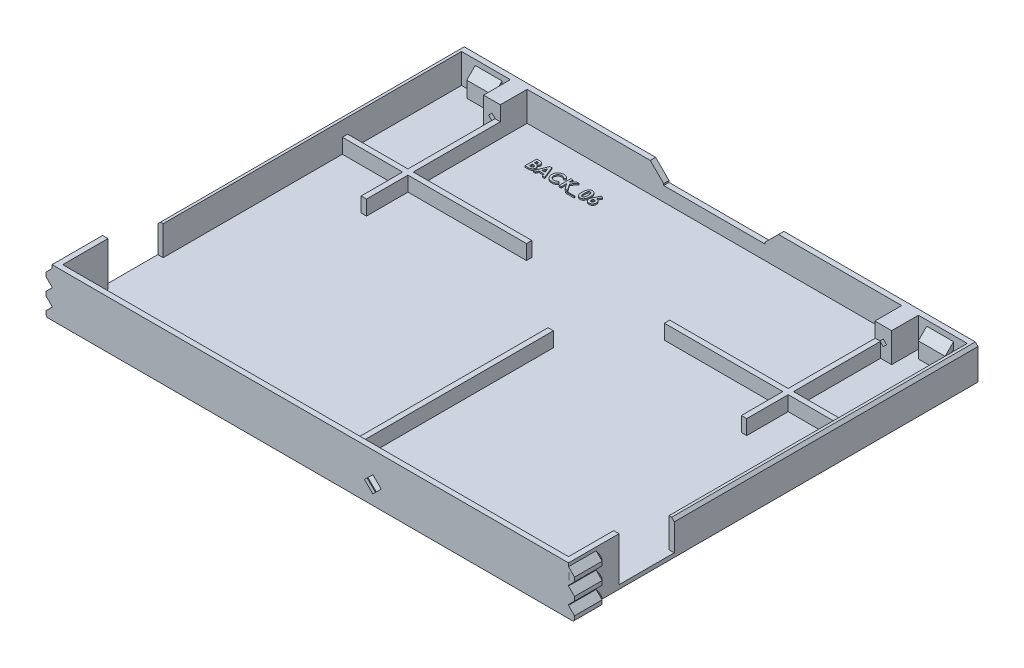
SolidWorks part; units mm, degrees
ref_plane "Front Plane" through (0, 0, 0) normal (0, 0, 1) x (1, 0, 0)
ref_plane "Top Plane" through (0, 0, 0) normal (0, 1, 0) x (1, 0, 0)
ref_plane "Right Plane" through (0, 0, 0) normal (1, 0, 0) x (0, 0, -1)
sketch "Sketch1" plane through (0, 0, 0) normal (0, 1, 0) x (1, 0, 0)
  line L3 (-77.15, -61.17) -> (77.15, -61.17)
  line L5 (-77.15, 61.17) -> (77.15, -61.17) construction
  line L6 (-77.15, -61.17) -> (77.15, 61.17) construction
  line L13 (-77.15, 61.17) -> (-77.15, -61.17)
  line L18 (77.15, 61.17) -> (-77.15, 61.17)
  line L20 (77.15, 61.17) -> (77.15, -61.17)
  point P0 (0, 0)
  point P6 (0, 0)
  dimension "D3" = 154.3
  dimension "D1" = 154.3
  dimension "D2" = 122.34
extrude "flat_on_wall" add sketch "Sketch1" along normal blind 1.2
sketch "Sketch3" plane through (0, 0, 0) normal (0, 1, 0) x (1, 0, 0)
  line L0 (-77.15, -29.57) -> (-77.15, 61.17)
  line L1 (-77.15, 61.17) -> (-77.15, -61.17) construction
  line L2 (-77.15, 61.17) -> (-45.55, 61.17)
  line L3 (77.15, 61.17) -> (-77.15, 61.17) construction
  line L6 (-75.55, 59.57) -> (-75.55, -29.57)
  line L7 (-75.55, -29.57) -> (-77.15, -29.57)
  line L8 (45.55, 61.17) -> (77.15, 61.17)
  line L9 (77.15, 61.17) -> (77.15, -29.57)
  line L10 (77.15, -61.17) -> (77.15, 61.17) construction
  line L11 (77.15, -29.57) -> (75.55, -29.57)
  line L12 (75.55, -29.57) -> (75.55, 59.57)
  line L15 (-77.15, -46.07) -> (-77.15, -61.17)
  line L16 (-77.15, -61.17) -> (77.15, -61.17)
  line L17 (77.15, -61.17) -> (77.15, -46.07)
  line L18 (77.15, -46.07) -> (75.55, -46.07)
  line L19 (75.55, -46.07) -> (75.55, -59.57)
  line L20 (75.55, -59.57) -> (-75.55, -59.57)
  line L21 (-75.55, -59.57) -> (-75.55, -46.07)
  line L22 (-75.55, -46.07) -> (-77.15, -46.07)
  line L23 (-75.55, 59.57) -> (-60.95, 59.57)
  line L24 (-60.95, 59.57) -> (-60.95, 51.57)
  line L25 (-60.95, 51.57) -> (-55.95, 51.57)
  line L26 (-55.95, 51.57) -> (-55.95, 59.57)
  line L27 (-55.95, 59.57) -> (-45.55, 59.57)
  line L28 (75.55, 59.57) -> (60.95, 59.57)
  line L29 (60.95, 59.57) -> (60.95, 51.57)
  line L30 (60.95, 51.57) -> (55.95, 51.57)
  line L31 (55.95, 51.57) -> (55.95, 59.57)
  line L32 (55.95, 59.57) -> (45.55, 59.57)
  line L34 (-45.55, 59.57) -> (45.55, 59.57)
  line L36 (-45.55, 61.17) -> (45.55, 61.17)
  point P25 (-76.35, -46.07)
  dimension "D2" = 1.6
  dimension "D3" = 30
  dimension "D4" = 16.5
  dimension "D5" = 5
  dimension "D6" = 1.6
  dimension "D7" = 30
  dimension "D8" = 16.5
  dimension "D9" = 1.6
  dimension "D10" = 13.5
  dimension "D11" = 1.6
  dimension "D12" = 1.6
  dimension "D13" = 13.5
  dimension "D14" = 14.6
  dimension "D15" = 5
  dimension "D16" = 8
  dimension "D17" = 8
  dimension "D18" = 8
  dimension "D19" = 8
  dimension "D20" = 1.6
  dimension "D21" = 14.6
  dimension "D22" = 1.6
  dimension "D23" = 1.6
extrude "walls" add sketch "Sketch3" along normal blind 10
sketch "Sketch5" plane through (0, 0, 0) normal (1, 0, 0) x (0, 0, -1)
  line L0 (-61.17, 10) -> (-61.17, 0) construction
  line L5 (-61.17, 0) -> (-51.97, 0)
  line L6 (-61.17, 0) -> (-61.17, 2)
  line L7 (-61.17, 2) -> (-51.97, 2)
  line L8 (-51.97, 0) -> (-51.97, 2)
  line L9 (-61.17, 0) -> (61.17, 0) construction
  line L10 (-61.17, 10) -> (-51.97, 10)
  line L11 (-61.17, 5) -> (-51.97, 5)
  line L12 (-61.17, 5) -> (-61.17, 7)
  line L13 (-61.17, 7) -> (-51.97, 7)
  line L14 (-51.97, 5) -> (-51.97, 7)
  line L15 (-61.17, 10) -> (-61.17, 12)
  line L16 (-61.17, 12) -> (-51.97, 12)
  line L17 (-51.97, 10) -> (-51.97, 12)
  line L18 (-61.17, 10) -> (-46.07, 10) construction
  dimension "D1" = 0
  dimension "D2" = 9.2
  dimension "D3" = 2
  dimension "D4" = 9.2
  dimension "D5" = 2
  dimension "D6" = 3
  dimension "D7" = 2
extrude "rails" add sketch "Sketch5" along normal blind 0.75 from surface starting at face at (77.15, 5.3, 18.91)
sketch "Sketch6" plane through (0, 0, 0) normal (1, 0, 0) x (0, 0, -1)
  line L0 (-61.17, 12) -> (-51.97, 12)
  line L1 (-61.17, 2) -> (-51.97, 2)
  line L2 (-61.17, 2) -> (-61.17, 0)
  line L3 (-61.17, 0) -> (-51.97, 0)
  line L4 (-51.97, 2) -> (-51.97, 0)
  line L5 (-61.17, 7) -> (-51.97, 7)
  line L6 (-61.17, 7) -> (-61.17, 5)
  line L7 (-61.17, 5) -> (-51.97, 5)
  line L8 (-51.97, 7) -> (-51.97, 5)
  line L9 (-61.17, 12) -> (-61.17, 10)
  line L10 (-61.17, 10) -> (-51.97, 10)
  line L11 (-51.97, 12) -> (-51.97, 10)
  dimension "D1" = 9.2
  dimension "D2" = 9.2
  dimension "D3" = 2
  dimension "D4" = 2
  dimension "D5" = 2
extrude "rails-left" add sketch "Sketch6" along normal blind 0.1 and the other way blind 1.8 from surface starting at face at (-77.15, 5.3, 18.91)
sketch "Sketch7" plane through (0, 0, 0) normal (0, 1, 0) x (1, 0, 0)
  line L0 (-47.15, 46.17) -> (-47.15, 39.9043) construction
  line L1 (-44.69, 46.17) -> (-44.69, 43.37)
  line L2 (-49.61, 46.17) -> (-49.61, 43.37)
  line L3 (77.15, 61.17) -> (-77.15, 61.17) construction
  line L4 (-77.15, -29.57) -> (-77.15, -46.07) construction
  line L5 (47.15, 46.17) -> (47.15, 39.9043) construction
  line L6 (49.61, 46.17) -> (49.61, 43.37)
  line L7 (44.69, 46.17) -> (44.69, 43.37)
  line L9 (77.15, -29.57) -> (77.15, 61.17) construction
  line L10 (77.15, 61.17) -> (-77.15, 61.17) construction
  line L13 (-77.05, -61.17) -> (77.15, -61.17) construction
  line L14 (-0.45, 8.83) -> (-0.45, 2.5643) construction
  line L15 (2.01, 8.83) -> (2.01, 6.03)
  line L16 (-2.91, 8.83) -> (-2.91, 6.03)
  line L17 (77.15, -46.07) -> (77.15, -29.57) construction
  arc A0 (-44.69, 46.17) -> (-49.61, 46.17) centre (-47.15, 46.17) ccw
  arc A3 (-44.69, 43.37) -> (-49.61, 43.37) centre (-47.15, 39.9043) cw
  arc A4 (49.61, 46.17) -> (44.69, 46.17) centre (47.15, 46.17) ccw
  arc A5 (49.61, 43.37) -> (44.69, 43.37) centre (47.15, 39.9043) cw
  arc A8 (2.01, 8.83) -> (-2.91, 8.83) centre (-0.45, 8.83) ccw
  arc A9 (2.01, 6.03) -> (-2.91, 6.03) centre (-0.45, 2.5643) cw
  point P2 (-47.9176, 44.8712)
  point P13 (43.1175, 41.9506)
  dimension "D1" = 15
  dimension "D5" = 2.46
  dimension "D9" = 4.25
  dimension "D2" = 30
  dimension "D3" = 15
  dimension "D4" = 30
  dimension "D6" = 6.2657
  dimension "D7" = 77.6
  dimension "D8" = 70
extrude "Cut-Extrude7" [suppressed] cut sketch "Sketch7" against normal through all from surface starting at face at (0, 1.2, -7.1)
sketch "Sketch8" plane through (0, 0, -51.57) normal (0, 0, 1) x (1, 0, 0)
  line L0 (-60.95, 10) -> (-60.95, 1.2) construction
  line L1 (-60.95, 10) -> (-55.95, 10) construction
  line L2 (55.95, 10) -> (55.95, 1.2) construction
  line L3 (55.95, 10) -> (60.95, 10) construction
  line L4 (-75.55, 10) -> (-60.95, 10) construction
  line L5 (-63.45, 3) -> (-71.45, 3)
  line L6 (-63.45, 3) -> (-63.45, 8)
  line L7 (-63.45, 8) -> (-71.45, 8)
  line L8 (-71.45, 3) -> (-71.45, 8)
  line L9 (-60.95, 1.2) -> (-75.55, 1.2) construction
  line L10 (-75.55, 10) -> (-75.55, 1.2) construction
  line L11 (-75.55, 10) -> (-75.55, 1.2)
  line L12 (-75.55, 1.2) -> (0, 1.2)
  line L13 (0, 1.2) -> (0, 10)
  line L14 (71.45, 3) -> (71.45, 8)
  line L15 (63.45, 8) -> (71.45, 8)
  line L16 (63.45, 3) -> (63.45, 8)
  line L17 (63.45, 3) -> (71.45, 3)
  line L18 (-58.45, 6.6) -> (-59.45, 5.6)
  line L19 (-59.45, 5.6) -> (-58.45, 4.6)
  line L20 (-58.45, 4.6) -> (-57.45, 5.6)
  line L21 (-57.45, 5.6) -> (-58.45, 6.6)
  line L22 (58.45, 6.6) -> (59.45, 5.6)
  line L23 (59.45, 5.6) -> (58.45, 4.6)
  line L24 (58.45, 4.6) -> (57.45, 5.6)
  line L25 (57.45, 5.6) -> (58.45, 6.6)
  circle A0 centre (-58.45, 5.6) radius 1 construction
  circle A1 centre (58.45, 5.6) radius 1 construction
  circle A2 centre (58.45, 5.6) radius 1 construction
  dimension "D1" = 2.5
  dimension "D3" = 2.5
  dimension "D2" = 4.4
  dimension "D4" = 4.4
  dimension "D5" = 5
  dimension "D6" = 8
  dimension "D7" = 5
  dimension "D8" = 2
  dimension "D9" = 1.8
  dimension "D10" = 75.55
extrude "Cut-Extrude8" cut sketch "Sketch8" against normal blind 10 contours A0 | A1 | L8 L5 L6 L7 | L16 L17 L14 L15 | L18 L19 L20 L21 | L24 L25 L22 L23 region at (-67.45, 5.5, -51.57) region at (67.45, 5.5, -51.57)
sketch "Sketch9" plane through (0, 1.2, 0) normal (0, 1, 0) x (1, 0, 0)
  line L0 (-75.55, 59.57) -> (-75.55, -29.57) construction
  line L7 (0.05, -59.57) -> (0.05, 37.2031)
  line L8 (-75.55, -59.57) -> (75.55, -59.57) construction
  line L9 (75.55, -59.57) -> (75.55, -46.07) construction
  line L12 (-55.95, 51.57) -> (-57.55, 51.57)
  line L13 (-55.95, 51.57) -> (-55.95, 25.5612)
  line L14 (-55.95, 11.57) -> (-57.55, 11.57)
  line L15 (-57.55, 51.57) -> (-57.55, 25.5612)
  line L16 (-75.55, 25.5612) -> (-57.55, 25.5612)
  line L17 (-75.55, 25.5612) -> (-75.55, 23.9612)
  line L18 (-75.55, 23.9612) -> (-57.55, 23.9612)
  line L19 (-20.55, 25.5612) -> (-20.55, 23.9612)
  line L20 (-55.95, 25.5612) -> (-20.55, 25.5612)
  line L21 (-55.95, 23.9612) -> (-20.55, 23.9612)
  line L22 (-55.95, 23.9612) -> (-55.95, 11.57)
  line L23 (-57.55, 23.9612) -> (-57.55, 11.57)
  line L24 (57.65, 23.9612) -> (57.65, 11.57)
  line L25 (56.05, 23.9612) -> (56.05, 11.57)
  line L26 (56.05, 23.9612) -> (20.65, 23.9612)
  line L27 (56.05, 25.5612) -> (20.65, 25.5612)
  line L28 (20.65, 25.5612) -> (20.65, 23.9612)
  line L29 (75.65, 23.9612) -> (57.65, 23.9612)
  line L30 (75.65, 25.5612) -> (75.65, 23.9612)
  line L31 (75.65, 25.5612) -> (57.65, 25.5612)
  line L32 (57.65, 51.57) -> (57.65, 25.5612)
  line L33 (56.05, 11.57) -> (57.65, 11.57)
  line L34 (56.05, 51.57) -> (56.05, 25.5612)
  line L35 (56.05, 51.57) -> (57.65, 51.57)
  line L36 (-75.55, -59.57) -> (75.55, -59.57) construction
  line L37 (4.45, -59.57) -> (6.05, -59.57)
  line L38 (4.45, -59.57) -> (4.45, 5.43)
  line L39 (4.45, 5.43) -> (6.05, 5.43)
  line L40 (6.05, -59.57) -> (6.05, 5.43)
  line L41 (-75.55, 59.57) -> (-75.55, -29.57) construction
  line L42 (-55.95, 51.57) -> (-60.95, 51.57) construction
  point P39 (5.25, 5.43)
  point P42 (-56.75, 11.57)
  line M17 (-75.55, -59.57) -> (75.55, -59.57)
  line M22 (75.55, -29.57) -> (75.55, 59.57)
  line M25 (60.95, 51.57) -> (55.95, 51.57)
  line M29 (-55.95, 51.57) -> (-60.95, 51.57)
  line M32 (-75.55, 59.57) -> (-75.55, -29.57)
  dimension "D1" = 1.6
  dimension "D2" = 6
  dimension "D3" = 75.5
  dimension "D4" = 1.6
  dimension "D5" = 1.6
  dimension "D6" = 65
  dimension "D7" = 55
  dimension "D8" = 40
extrude "Boss-Extrude8" add sketch "Sketch9" along normal blind 4.4 contours L18 L23 L14 L22 L21 L19 L20 L13 L15 L16 M29 M32 | L40 L39 L38 M17 | L34 L27 L28 L26 L25 L33 L24 L29 L31 L32 M25 M22 region at (-56.6301, 1.2, -38.5656) region at (56.9707, 1.2, -17.7656) region at (5.25, 1.2, 27.07)
sketch "Sketch16" plane through (0, 10, 0) normal (0, 1, 0) x (1, 0, 0)
  line L2 (77.15, -61.17) -> (77.15, -46.07)
  line L3 (77.15, -46.07) -> (75.55, -46.07)
  line L4 (75.55, -46.07) -> (75.55, -59.57)
  line L5 (75.55, -59.57) -> (-75.55, -59.57)
  line L6 (-75.55, -59.57) -> (-75.55, -46.07)
  line L7 (-75.55, -46.07) -> (-77.15, -46.07)
  line L8 (-77.15, -46.07) -> (-77.15, -61.17)
  line L11 (-77.15, -61.17) -> (77.15, -61.17)
extrude "Boss-Extrude9" add sketch "Sketch16" along normal blind 4.4
chamfer "Rail Chamfers" distance 0.8 angle 45 10 edges at (77.525, 7, 51.97) (77.525, 5, 51.97) (77.525, 2, 51.97) (77.525, 0, 51.97) (-78.05, 12, 51.97) (-78.05, 10, 51.97) (-78.05, 7, 51.97) (-78.05, 5, 51.97) (-78.05, 2, 51.97) (-78.05, 0, 51.97)
chamfer "Rail Chamfers 2" distance 0.8 angle 45 2 edges at (77.525, 12, 51.97) (77.525, 10, 51.97)
chamfer "Wall Chamfers" distance 0.8 angle 45 2 edges at (77.15, 10, -15.8) (-77.15, 10, -15.8)
sketch "Sketch18" plane through (0, 0, -61.17) normal (0, 0, -1) x (-1, 0, 0)
  line L0 (-76.35, 10) -> (76.35, 10) construction
  line L1 (-15.15, 10) -> (15.15, 10)
  line L2 (-15.15, 10) -> (-15.15, 5.5)
  line L3 (-15.15, 5.5) -> (15.15, 5.5)
  line L4 (15.15, 10) -> (15.15, 5.5)
  line L5 (-77.15, 9.2) -> (-77.15, 0) construction
  line L6 (77.15, 9.2) -> (77.15, 0) construction
  dimension "D1" = 62
  dimension "D2" = 62
  dimension "D3" = 4.5
extrude "Ribbon Hole" cut sketch "Sketch18" against normal blind 10
chamfer "Chamfer1" distance 0.4 angle 45 30 edges at (-78.95, 10.4, 52.37) (-78.95, 11, 51.97) (-78.95, 11.6, 52.37) (-78.95, 12, 56.97) (-78.95, 11, 61.17) (-78.95, 10, 56.97) (-78.95, 5.4, 52.37) (-78.95, 6, 51.97) (-78.95, 6.6, 52.37) (-78.95, 7, 56.97) (-78.95, 6, 61.17) (-78.95, 5, 56.97) (-78.95, 0.4, 52.37) (-78.95, 1, 51.97) (-78.95, 1.6, 52.37) (-78.95, 2, 56.97) (-78.95, 1, 61.17) (-78.95, 0, 56.97) (77.9, 1.6, 52.37) (77.9, 1, 51.97) (77.9, 0.4, 52.37) (77.9, 0, 56.97) (77.9, 2, 56.97) (77.9, 1, 61.17) (77.9, 6, 61.17) (77.9, 5, 56.97) (77.9, 5.4, 52.37) (77.9, 6, 51.97) (77.9, 6.6, 52.37) (77.9, 7, 56.97)
chamfer "Chamfer2" distance 0.4 angle 45 6 edges at (77.9, 11, 51.97) (77.9, 10.4, 52.37) (77.9, 10, 56.97) (77.9, 11, 61.17) (77.9, 11.6, 52.37) (77.9, 12, 56.97)
sketch "Sketch19" plane through (0, 0, 61.17) normal (0, 0, 1) x (1, 0, 0)
  line L0 (-78.55, 0) -> (77.5, 0) construction
  line L2 (16.2, 5.5) -> (16.2, 14.5133) construction
  line L3 (21.2, 5.5) -> (21.2, 14.5133) construction
  line L4 (16.2, 14.5133) -> (21.2, 14.5133) construction
  line L6 (18.7, 3) -> (16.2, 5.5)
  line L7 (18.7, 3) -> (21.2, 5.5)
  line L8 (21.2, 5.5) -> (18.7, 8)
  line L9 (18.7, 8) -> (16.2, 5.5)
  arc A0 (16.2, 5.5) -> (21.2, 5.5) centre (18.7, 5.5) ccw construction
  dimension "D1" = 5.5
  dimension "D3" = 5
  dimension "D2" = 18.7
extrude "Cut-Extrude9" cut sketch "Sketch19" against normal blind 10
sketch "Sketch20" plane through (0, 0, 61.17) normal (0, 0, 1) x (1, 0, 0)
  line L0 (-78.95, 11.6) -> (-78.95, 10.4)
  line L1 (-78.95, 10.4) -> (-77.05, 8.5)
  line L2 (-78.95, 11.6) -> (-77.15, 13.4)
  line L4 (-77.15, 14.4) -> (-77.15, 12) construction
  line L7 (-78.95, 1.6) -> (-77.05, 3.5)
  line L9 (-78.95, 5.4) -> (-77.05, 3.5)
  line L10 (-78.95, 6.6) -> (-78.95, 5.4)
  line L11 (-78.95, 6.6) -> (-77.05, 8.5)
  line L12 (-78.95, 1.6) -> (-78.95, 0.4)
  line L13 (-78.95, 0.4) -> (-78.55, 0)
  line L15 (-78.55, 10) -> (-78.95, 10.4) construction
  line L16 (-77.15, 13.4) -> (-76.932, 13.4)
  line L19 (-78.55, 0) -> (-76.932, 0)
  line L22 (-78.55, 7) -> (-78.95, 6.6) construction
  line L23 (-76.932, 13.4) -> (-76.932, 0)
extrude "Boss-Extrude11" add sketch "Sketch20" against normal blind 9.25
sketch "Sketch21" plane through (-71.45, 0, 0) normal (1, 0, 0) x (0, 0, -1)
  line L0 (61.17, 8) -> (58.4281, 5.2665)
  line L1 (58.4281, 5.2665) -> (58.4281, 1.2)
  line L2 (59.57, 1.2) -> (25.5612, 1.2) construction
  line L3 (57.0393, 1.2) -> (57.0393, 5.8819)
  line L4 (57.0393, 5.8819) -> (61.17, 10)
  line L6 (58.4281, 1.2) -> (57.0393, 1.2)
  line L7 (61.17, 10) -> (61.17, 8)
extrude "Boss-Extrude17" add sketch "Sketch21" along normal blind 8
mirror "Mirror2" about plane through (0, 0, 0) normal (1, 0, 0) of "Boss-Extrude17", "Boss-Extrude11"
chamfer "Chamfer3" distance 1 angle 45 18 edges at (-78.75, 0.2, 51.92) (-78.95, 1, 51.92) (-78.05, 2.5, 51.92) (-78.05, 4.5, 51.92) (-78.95, 6, 51.92) (-78.05, 7.5, 51.92) (-78.05, 9.5, 51.92) (-78.95, 11, 51.92) (-78.05, 12.5, 51.92) (78.75, 0.2, 51.92) (78.95, 1, 51.92) (78.05, 2.5, 51.92) (78.05, 4.5, 51.92) (78.95, 6, 51.92) (78.05, 7.5, 51.92) (78.05, 9.5, 51.92) (78.95, 11, 51.92) (78.05, 12.5, 51.92)
chamfer "Chamfer4" distance 4 angle 45 2 edges at (15.15, 10, -60.37) (-15.15, 10, -60.37)
sketch "Sketch22" plane through (0, 1.2, 0) normal (0, 1, 0) x (1, 0, 0)
  text T0 "<b>BACK_06</b>"
extrude "Boss-Extrude18" add sketch "Sketch22" along normal blind 0.4
chamfer "Chamfer5" distance 0.8 angle 45 4 edges at (19.95, 6.75, 59.57) (19.95, 4.25, 59.57) (17.45, 4.25, 59.57) (17.45, 6.75, 59.57)
